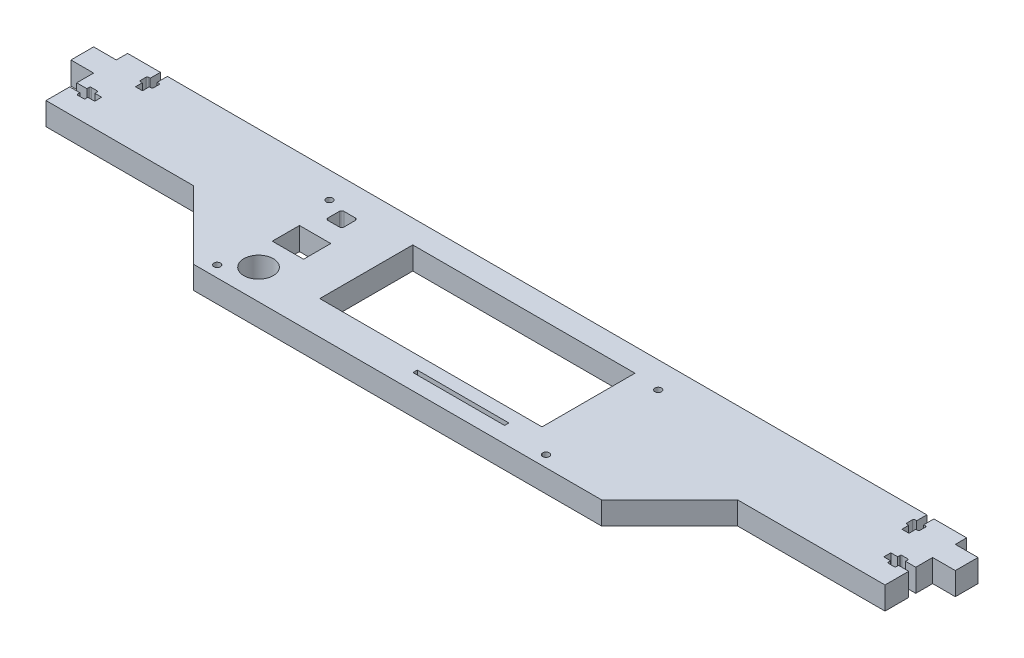
SolidWorks part; units mm, degrees
ref_plane "Front Plane" through (0, 0, 0) normal (0, 0, 1) x (1, 0, 0)
ref_plane "Top Plane" through (0, 0, 0) normal (0, 1, 0) x (1, 0, 0)
ref_plane "Right Plane" through (0, 0, 0) normal (1, 0, 0) x (0, 0, -1)
sketch "Sketch1" plane through (0, 0, 0) normal (0, 1, 0) x (1, 0, 0)
  line L0 (0, 18) -> (0, -18) construction
  line L1 (-185, 18) -> (0, 18)
  line L2 (-185, 18) -> (-185, 13)
  line L3 (-185, -18) -> (0, -18)
  line L4 (0, 18) -> (0, -18)
  line L5 (-185, 18) -> (0, 0) construction
  line L6 (-185, -18) -> (0, 0) construction
  line L7 (-185, 13) -> (-195, 13)
  line L8 (-195, 13) -> (-195, 3)
  line L9 (-195, 3) -> (-185, 3)
  line L10 (-185, 3) -> (-185, -18)
  point P0 (0, 0)
  dimension "D6" = 10
  dimension "D7" = 10
  dimension "D1" = 185
  dimension "D2" = 36
  dimension "D4" = 5
  dimension "D9" = 18
extrude "MainShape" add sketch "Sketch1" along normal blind 10 contours L2 L7 L8 L9 region at (-93.9423, 0, -0.1183)
sketch "Sketch2" plane through (0, 10, 0) normal (0, 1, 0) x (1, 0, 0)
  line L0 (-169, 18) -> (-169, 7) construction
  line L1 (-185, 18) -> (0, 18) construction
  line L2 (-170.55, 18) -> (-170.55, 13.5)
  line L3 (-170.55, 13.5) -> (-171.35, 13.5)
  line L4 (-171.85, 13) -> (-171.85, 10.5)
  line L5 (-171.35, 10) -> (-170.55, 10)
  line L6 (-170.55, 10) -> (-170.55, 7)
  line L7 (-170.55, 7) -> (-167.45, 7)
  line L8 (-185, 18) -> (-185, 13) construction
  line L9 (-170.55, 18) -> (-167.45, 18)
  line L10 (-167.45, 10) -> (-167.45, 7)
  line L11 (-166.65, 10) -> (-167.45, 10)
  line L12 (-166.15, 13) -> (-166.15, 10.5)
  line L13 (-167.45, 13.5) -> (-166.65, 13.5)
  line L14 (-167.45, 18) -> (-167.45, 13.5)
  line L16 (-185, -6) -> (-174, -6) construction
  line L50 (-185, 3) -> (-185, -18) construction
  line L51 (-174, -7.55) -> (-174, -4.45)
  line L52 (-174, -4.45) -> (-177, -4.45)
  line L53 (-177, -4.45) -> (-177, -3.5)
  line L54 (-177.5, -3) -> (-180, -3)
  line L55 (-180.5, -3.5) -> (-180.5, -4.45)
  line L56 (-180.5, -4.45) -> (-185, -4.45)
  line L57 (-185, -4.45) -> (-185, -7.55)
  line L58 (-195, 13) -> (-195, 3) construction
  line L59 (-180.5, -7.55) -> (-185, -7.55)
  line L60 (-180.5, -8.5) -> (-180.5, -7.55)
  line L61 (-177.5, -9) -> (-180, -9)
  line L62 (-177, -7.55) -> (-177, -8.5)
  line L63 (-174, -7.55) -> (-177, -7.55)
  arc A0 (-171.85, 10.5) -> (-171.35, 10) centre (-171.35, 10.5) ccw
  arc A1 (-171.35, 13.5) -> (-171.85, 13) centre (-171.35, 13) ccw
  arc A2 (-166.65, 13.5) -> (-166.15, 13) centre (-166.65, 13) cw
  arc A3 (-166.15, 10.5) -> (-166.65, 10) centre (-166.65, 10.5) cw
  arc A16 (-177, -3.5) -> (-177.5, -3) centre (-177.5, -3.5) ccw
  arc A17 (-180, -3) -> (-180.5, -3.5) centre (-180, -3.5) ccw
  arc A18 (-180, -9) -> (-180.5, -8.5) centre (-180, -8.5) cw
  arc A19 (-177, -8.5) -> (-177.5, -9) centre (-177.5, -8.5) cw
  point P14 (-171.85, 10)
  point P17 (-171.85, 13.5)
  point P28 (-166.15, 13.5)
  point P29 (-166.15, 10)
  point P34 (-195, 8)
  point P45 (-177, -3)
  point P48 (-180.5, -3)
  dimension "D8" = 0.5
  dimension "D16" = 0.5
  dimension "D1" = 11
  dimension "D2" = 1.55
  dimension "D3" = 1.55
  dimension "D4" = 8
  dimension "D5" = 2.85
  dimension "D6" = 3.5
  dimension "D7" = 16
  dimension "D9" = 11
  dimension "D10" = 8
  dimension "D11" = 3.5
  dimension "D12" = 3
  dimension "D13" = 1.55
  dimension "D14" = 1.55
  dimension "D15" = 14
extrude "ScrewSlots" cut sketch "Sketch2" against normal through all
mirror "Mirror1" about plane through (0, 0, 0) normal (1, 0, 0) of "ScrewSlots", "MainShape"
sketch "Sketch6" plane through (0, 10, 0) normal (0, 1, 0) x (1, 0, 0)
  line L0 (0, -18) -> (0, -48) construction
  line L2 (-185, -18) -> (185, -18) construction
  line L3 (90, -48) -> (-90, -48)
  line L4 (-90, -48) -> (-120, -18)
  line L5 (90, -48) -> (120, -18)
  line L6 (-120, -18) -> (120, -18)
  dimension "D1" = 135
  dimension "D2" = 30
  dimension "D3" = 90
extrude "Boss-Extrude1" add sketch "Sketch6" against normal through all
sketch "Sketch8" plane through (0, 10, 0) normal (0, 1, 0) x (1, 0, 0)
  line L0 (-71.5, 4.8833) -> (-77.5, 4.8833) construction
  line L1 (-77, -1.6167) -> (-72, -1.6167)
  line L2 (-78, -0.6167) -> (-78, 4.3833)
  line L3 (-77, 5.3833) -> (-72, 5.3833)
  line L4 (-71, -0.6167) -> (-71, 4.3833)
  line L5 (-78, -1.6167) -> (-71, 5.3833) construction
  line L6 (-78, 5.3833) -> (-71, -1.6167) construction
  line L7 (-71.5, -1.1167) -> (-71.5, 4.8833) construction
  circle A0 centre (-74.5, -34.7667) radius 6.5
  circle A1 centre (-74.5, -15.8167) radius 5.5
  arc A2 (-77, -1.6167) -> (-78, -0.6167) centre (-77, -0.6167) cw
  circle A3 centre (-74.5, -34.7667) radius 6 construction
  circle A4 centre (-74.5, -15.8167) radius 3.5 construction
  arc A5 (-72, -1.6167) -> (-71, -0.6167) centre (-72, -0.6167) ccw
  arc A6 (-72, 5.3833) -> (-71, 4.3833) centre (-72, 4.3833) cw
  arc A7 (-78, 4.3833) -> (-77, 5.3833) centre (-77, 4.3833) cw
  point P6 (-74.5, 1.8833)
  dimension "D1" = 0.5
  dimension "D2" = 2
  dimension "D3" = 0.5
  dimension "D5" = 1
  dimension "D4" = 0.5
extrude "Cut-Extrude2" cut sketch "Sketch8" against normal through all
sketch "Sketch7" plane through (0, 10, 0) normal (0, 1, 0) x (1, 0, 0)
  circle A0 centre (60.5, -43.0167) radius 1.45
  circle A1 centre (-84.5, -43.0167) radius 1.45
  circle A2 centre (-84.5, 6.4833) radius 1.45
  circle A3 centre (60.5, 6.4833) radius 1.45
  dimension "D1" = 2.9
  dimension "D2" = 2.9
  dimension "D3" = 2.9
  dimension "D4" = 2.9
extrude "Cut-Extrude1" cut sketch "Sketch7" against normal through all
sketch "Sketch9" plane through (0, 10, 0) normal (0, 1, 0) x (1, 0, 0)
  line L0 (0, 7.2333) -> (0, -32.7667) construction
  line L1 (48.5, 7.2333) -> (-48.5, 7.2333) construction
  line L2 (-48.5, -32.7667) -> (48.5, -32.7667) construction
  line L3 (-48.5, -12.7667) -> (48.5, -12.7667) construction
  line L4 (-48.5, 7.2333) -> (-48.5, -32.7667) construction
  line L5 (48.5, -32.7667) -> (48.5, 7.2333) construction
  line L7 (-49, -33.2667) -> (49, -33.2667)
  line L8 (-49, -33.2667) -> (-49, 7.7333)
  line L9 (-49, 7.7333) -> (49, 7.7333)
  line L10 (49, -33.2667) -> (49, 7.7333)
  line L11 (-49, -33.2667) -> (49, 7.7333) construction
  line L12 (-49, 7.7333) -> (49, -33.2667) construction
  point P12 (0, -12.7667)
  dimension "D1" = 0.5
  dimension "D2" = 0.5
extrude "Cut-Extrude3" cut sketch "Sketch9" against normal through all and the other way through all
sketch "Sketch10" plane through (0, 10, 0) normal (0, 1, 0) x (1, 0, 0)
  line L0 (20, -39.2667) -> (20, -40.7667) construction
  line L1 (40, -39.2667) -> (0, -39.2667) construction
  line L2 (0, -40.7667) -> (40, -40.7667) construction
  line L3 (0, -40.0167) -> (40, -40.0167) construction
  line L4 (0, -39.2667) -> (0, -40.7667) construction
  line L5 (40, -40.7667) -> (40, -39.2667) construction
  line L7 (-0.2, -40.9667) -> (40.2, -40.9667)
  line L8 (-0.2, -40.9667) -> (-0.2, -39.0667)
  line L9 (-0.2, -39.0667) -> (40.2, -39.0667)
  line L10 (40.2, -40.9667) -> (40.2, -39.0667)
  line L11 (-0.2, -40.9667) -> (40.2, -39.0667) construction
  line L12 (-0.2, -39.0667) -> (40.2, -40.9667) construction
  point P12 (20, -40.0167)
  dimension "D1" = 0.2
  dimension "D2" = 0.2
extrude "Cut-Extrude4" cut sketch "Sketch10" against normal through all
sketch "Sketch12" plane through (0, 0, 0) normal (0, -1, 0) x (-1, 0, 0)
  line L1 (81.4, -9.8167) -> (67.6, -9.8167)
  line L2 (81.4, -9.8167) -> (81.4, -21.8167)
  line L3 (81.4, -21.8167) -> (67.6, -21.8167)
  line L4 (67.6, -9.8167) -> (67.6, -21.8167)
  line L5 (81.4, -9.8167) -> (67.6, -21.8167) construction
  line L6 (81.4, -21.8167) -> (67.6, -9.8167) construction
  point P0 (74.5, -15.8167)
  dimension "D1" = 13.8
  dimension "D2" = 12
extrude "PotentiometerAdjustment" cut sketch "Sketch12" against normal through all
sketch "Sketch11" [suppressed] plane through (0, 0, 0) normal (0, -1, 0) x (1, 0, 0)
  line L1 (-149.5, -2.5) -> (-167.5, -2.5)
  line L2 (-147.5, -0.5) -> (-147.5, 6.5)
  line L3 (-149.5, 8.5) -> (-167.5, 8.5)
  line L4 (-169.5, -0.5) -> (-169.5, 6.5)
  line L5 (-147.5, -2.5) -> (-169.5, 8.5) construction
  line L6 (-147.5, 8.5) -> (-169.5, -2.5) construction
  line L7 (170.75, -7.5) -> (167.25, -7.5) construction
  line L8 (-174.5, 7.75) -> (-174.5, 4.25) construction
  arc A0 (-147.5, 6.5) -> (-149.5, 8.5) centre (-149.5, 6.5) ccw
  arc A1 (-167.5, 8.5) -> (-169.5, 6.5) centre (-167.5, 6.5) ccw
  arc A2 (-167.5, -2.5) -> (-169.5, -0.5) centre (-167.5, -0.5) cw
  arc A3 (-149.5, -2.5) -> (-147.5, -0.5) centre (-149.5, -0.5) ccw
  point P0 (-158.5, 3)
  dimension "D3" = 2
  dimension "D1" = 22
  dimension "D2" = 11
  dimension "D4" = 5
  dimension "D5" = 5
extrude "LCDCableCutout" [suppressed] cut sketch "Sketch11" against normal through all
equation "\"Y-ROD-SPACING\"=75"
equation "\"Y-BED-OFFSET\"=2"
equation "\"Y-BED-ROD-INSET\"=3.5"
equation "\"T-SLOT-NUT-FILLET-RADIUS\"=0.5"
equation "\"T-SLOT-SCREW-SHAFT-RADIUS\"=1.55"
equation "\"T-SLOT-SCREW-SHAFT-CUTOUT-LENGTH\"=11.0"
equation "\"T-SLOT-NUT-DEPTH\"=3.5"
equation "\"T-SLOT-NUT-WIDTH\"=2.85"
equation "\"T-SLOT-NUT-END-DISTANCE\"=8"
equation "\"ACRYLIC-TAB-CUTOUT-SIZE\"=\"ACRYLIC-THICKNESS\"+\"ACRYLIC-TAB-TOLERANCE\"*2"
equation "\"ACRYLIC-M3-HOLE\"=2.9"
equation "\"SMOOTHROD-CAP-SCREW-DISTANCE\"=20"
equation "\"D2@Sketch2\"=\"T-SLOT-SCREW-SHAFT-RADIUS\""
equation "\"D1@Sketch2\"=\"T-SLOT-SCREW-SHAFT-CUTOUT-LENGTH\""
equation "\"D6@Sketch2\"=\"T-SLOT-NUT-DEPTH\""
equation "\"D5@Sketch2\"=\"T-SLOT-NUT-WIDTH\""
equation "\"D3@Sketch2\"=\"T-SLOT-SCREW-SHAFT-RADIUS\""
equation "\"D8@Sketch2\"=\"T-SLOT-NUT-FILLET-RADIUS\""
equation "\"D4@Sketch2\"=\"T-SLOT-NUT-END-DISTANCE\""
equation "\"D11@Sketch2\"=\"T-SLOT-NUT-DEPTH\""
equation "\"D10@Sketch2\"=\"T-SLOT-NUT-END-DISTANCE\""
equation "\"D13@Sketch2\"=\"T-SLOT-SCREW-SHAFT-RADIUS\""
equation "\"D14@Sketch2\"=\"T-SLOT-SCREW-SHAFT-RADIUS\""
equation "\"D16@Sketch2\"=\"T-SLOT-NUT-FILLET-RADIUS\""
equation "\"D9@Sketch2\"=\"T-SLOT-SCREW-SHAFT-CUTOUT-LENGTH\""
equation "\"ACRYLIC-TAB-WIDTH\"=\"ACRYLIC-THICKNESS\""
equation "\"D6@Sketch1\"=\"ACRYLIC-TAB-WIDTH\""
equation "\"D7@Sketch1\"=\"ACRYLIC-TAB-WIDTH\""
equation "\"FRAME-WIDTH-INNER\"=370"
equation "\"D1@Sketch1\"=\"FRAME-WIDTH-INNER\"/2"
equation "\"X-ROD-SPACING\"=45"
equation "\"Z-ROD-SPACING\"=17.5"
equation "\"ACRYLIC-THICKNESS\"=10"
equation "\"ACRYLIC-THICKNESS2\"=4.5"
equation "\"NEMA17-HOLE-SPACING\"=31"
equation "\"NEMA17-CENTRAL-CUTOUT\"=22.5"
equation "\"Z-BRACKET-REACH\"=55"
equation "\"TOP-BRACKET-SPACING\"=40"
equation "\"SMOOTHROD-X-LENGTH\"=350"
equation "\"SMOOTHROD-Y-LENGTH\"=350"
equation "\"SMOOTHROD-Z-LENGTH\"=350"
equation "\"SMOOTHROD-TIGHTENING-HEADROOM\"=.25"
equation "\"LEADSCREW-Z-LENGTH\"=300"
equation "\"SCREW-LENGTH-FRAME\"=\"ACRYLIC-THICKNESS\" + 10"
equation "\"SCREW-HEAD-RADIUS\"=6"
equation "\"PRINTED-X-SMOOTHROD-DIAMETER\"=8.4"
equation "\"PRINTED-X-SMOOTHROD-CUTOUT\"=10"
equation "\"PRINTED-X-BASE-HEIGHT\"=10"
equation "\"PRINTED-LM8UU-CUTOUT-SIZE\"=15.5"
equation "\"PRINTED-LM8UU-CUTOUT-LENGTH\"=24.5"
equation "\"PRINTED-X-IDLER-HEIGHT\"=16"
equation "\"PSU-MOUNTING-WIDTH\"=95"
equation "\"PSU-MOUNTING-HEIGHT\"=177"
equation "\"D1@MainShape\"=\"ACRYLIC-THICKNESS\""
equation "\"Y-BELT-TO-ROD-DISTANCE\"=20"
equation "\"SPOOL-HOLDER-ROD-SPACING\"=150"
equation "\"Z-ROD-INSET\"=16"
equation "\"D7@Sketch2\"=\"Z-ROD-INSET\""
equation "\"D1@Sketch7\"=\"ACRYLIC-M3-HOLE\""
equation "\"D2@Sketch7\"=\"ACRYLIC-M3-HOLE\""
equation "\"D3@Sketch7\"=\"ACRYLIC-M3-HOLE\""
equation "\"D4@Sketch7\"=\"ACRYLIC-M3-HOLE\""
equation "\"Y-BED-SCREW-SPACING\"=209"
equation "\"Y-BED-SCREW-CUTOUT-SLOT-HEIGHT\"=2"
equation "\"ACRYLIC-TAB-TOLERANCE\"=-.05"
equation "\"SCREW-LENGTH-MOTOR\"=\"ACRYLIC-THICKNESS\" + 5"
equation "\"SCREW-LENGTH-EXTRUDER\"=28"
equation "\"PRINTED-M3-HOLE\"=3.5"
equation "\"PRINTED-M3-NUT-AF\"=6.25"
equation "\"ACRYLIC-X-CARRIAGE-WIDTH\"=55"
equation "\"ACRYLIC-X-CARRIAGE-HEIGHT\"=75"
equation "\"ACRYLIC-X-CARRIAGE-LM8UU-CUTOUT-WIDTH\"=24.25"
equation "\"ACRYLIC-X-CARRIAGE-LM8UU-CUTOUT-HEIGHT\"=11.0"
equation "\"ACRYLIC-X-CARRIAGE-SCREW-SPACING-X\"=15"
equation "\"ACRYLIC-X-CARRIAGE-SCREW-SPACING-Y\"=33"
equation "\"ACRYLIC-X-CARRIAGE-CENTER-TAB-SPACING\"=14"
equation "\"ACRYLIC-X-CARRIAGE-EXTRUDER-OFFSET\"=26"
equation "\"ACRYLIC-X-CARRIAGE-EXTRUDER-ANGLE\"=90"
equation "\"ACRYLIC-X-CARRIAGE-EXTRUDER-SHELF-DEPTH\"=\"ACRYLIC-X-CARRIAGE-EXTRUDER-OFFSET\" + 28"
equation "\"ACRYLIC-X-CARRIAGE-EXTRUDER-BRACE-SPACING\"=23"
equation "\"ACRYLIC-X-CARRIAGE-EXTRUDER-BRACE-TAB-OFFSET\"=20"
equation "\"ACRYLIC-X-CARRIAGE-EXTRUDER-BRACE-HEIGHT\"=35"
equation "\"ACRYLIC-X-CARRIAGE-EXTRUDER-BRACE-SCREW-SPACING\"=22"
equation "\"ACRYLIC-X-CARRIAGE-DUAL-WIDTH-MULTIPLIER\"=1.65"
equation "\"ACRYLIC-X-CARRIAGE-DUAL-HOTEND-SPACING\"=42"
equation "\"ACRYLIC-X-CARRIAGE-DUAL-WIDTH\"=75"
equation "\"ACRYLIC-X-CARRIAGE-DUAL-HOTEND-SEPARATION\"=36"
equation "\"ACRYLIC-X-CARRIAGE-DUAL-MOUNT-PLATE-DEPTH\"=75"
equation "\"ACRYLIC-X-CARRIAGE-DUAL-MOUNT-BRACE-WIDTH\"=33"
equation "\"ACRYLIC-X-CARRIAGE-DUAL-MOUNT-SCREW-WIDTH\"=40"
equation "\"BLOWER-FAN-WIDTH\"=15"
